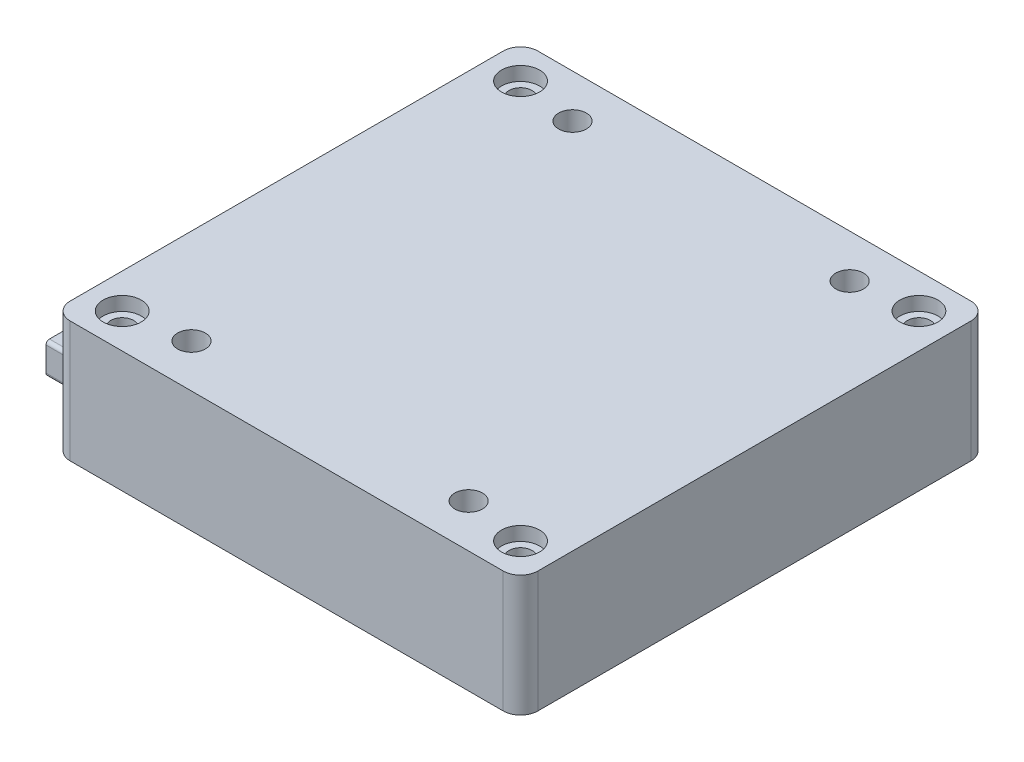
SolidWorks part; units mm, degrees
ref_plane "Front Plane" through (0, 0, 0) normal (0, 0, 1) x (1, 0, 0)
ref_plane "Top Plane" through (0, 0, 0) normal (0, 1, 0) x (1, 0, 0)
ref_plane "Right Plane" through (0, 0, 0) normal (1, 0, 0) x (0, 0, -1)
sketch "Sketch2" plane through (0, 0, 0) normal (0, 1, 0) x (1, 0, 0)
  line L1 (67.5, 67.5) -> (-67.5, 67.5)
  line L2 (67.5, 67.5) -> (67.5, -67.5)
  line L3 (67.5, -67.5) -> (-67.5, -67.5)
  line L4 (-67.5, 67.5) -> (-67.5, -67.5)
  line L5 (67.5, 67.5) -> (-67.5, -67.5) construction
  line L6 (67.5, -67.5) -> (-67.5, 67.5) construction
  point P0 (0, 0)
  dimension "D1" = 135
extrude "Boss-Extrude1" add sketch "Sketch2" along normal blind 35
fillet "Fillet1" radius 5 4 edges at (67.5, 17.5, -67.5) (67.5, 17.5, 67.5) (-67.5, 17.5, 67.5) (-67.5, 17.5, -67.5)
hole_wizard "CBORE for M6 Hex Head Bolt1" positions "3DSketch1" profile "Sketch6" counterbore size "M6" standard "DIN"
sketch3d "3DSketch1"
  line L0 (62.5, 35, -67.5) -> (-62.5, 35, -67.5) construction
  line L1 (-67.5, 35, -62.5) -> (-67.5, 35, 62.5) construction
  point P0 (-57.5, 35, -57.5)
  dimension "D1" = 10
  dimension "D2" = 10
sketch "Sketch6" plane through (-57.5, 35, -57.5) normal (1, 0, 0) x (0, 0, 1)
  line L0 (0, 0) -> (0, 43.9828)
  line L1 (0, 43.9828) -> (3.3, 42)
  line L2 (3.3, 42) -> (3.3, 4)
  line L3 (3.3, 4) -> (5.5, 4)
  line L4 (5.5, 4) -> (5.5, 0)
  line L5 (5.5, 0) -> (0, 0)
  line L10 (0, 43.9828) -> (-3.3, 42) construction
  line L11 (0, -6.35) -> (0, 107.95) construction
  dimension "Hole Dia." = 6.6
  dimension "Hole Depth" = 42
  dimension "C'Bore Dia." = 11
  dimension "C'Bore Depth" = 4
  dimension "Drill Angle" = 118
ref_axis "Axis1" through (0, -1.75, 0) along (0, 1, 0)
sketch "Sketch7" plane through (-67.5, 0, 0) normal (-1, 0, 0) x (0, 0, 1)
  line L0 (0, -1.75) -> (0, 36.75) construction
  line L1 (60, 19) -> (-60, 19)
  line L2 (60, 19) -> (60, 5)
  line L3 (60, 5) -> (-60, 5)
  line L4 (-60, 19) -> (-60, 5)
  line L5 (60, 19) -> (-60, 5) construction
  line L6 (60, 5) -> (-60, 19) construction
  line L7 (-62.5, 0) -> (62.5, 0) construction
  point P0 (0, 12)
  dimension "D1" = 5
  dimension "D2" = 120
  dimension "D3" = 14
extrude "Boss-Extrude2" add sketch "Sketch7" along normal blind 2 separate body
fillet "Fillet2" radius 2 4 edges at (-68.5, 5, -60) (-68.5, 5, 60) (-68.5, 19, 60) (-68.5, 19, -60)
sketch "Sketch9" plane through (-69.5, 0, 0) normal (-1, 0, 0) x (0, 0, 1)
  line L0 (0, 19) -> (0, 5) construction
  line L1 (58, 19) -> (-58, 19) construction
  line L2 (-58, 5) -> (58, 5) construction
  line L3 (56.5, 15.5) -> (-56.5, 15.5)
  line L4 (56.5, 16.5) -> (-56.5, 16.5)
  line L5 (57.5, 15.5) -> (57.5, 8.5)
  line L6 (56.5, 7.5) -> (-56.5, 7.5)
  line L7 (-57.5, 15.5) -> (-57.5, 8.5)
  line L8 (57.5, 16.5) -> (-57.5, 7.5) construction
  line L9 (57.5, 7.5) -> (-57.5, 16.5) construction
  line L10 (-56.5, 15.5) -> (-56.5, 8.5)
  line L11 (56.5, 8.5) -> (-56.5, 8.5)
  line L12 (56.5, 15.5) -> (56.5, 8.5)
  arc A0 (56.5, 16.5) -> (57.5, 15.5) centre (56.5, 15.5) cw
  arc A1 (57.5, 8.5) -> (56.5, 7.5) centre (56.5, 8.5) cw
  arc A2 (-56.5, 7.5) -> (-57.5, 8.5) centre (-56.5, 8.5) cw
  arc A3 (-56.5, 16.5) -> (-57.5, 15.5) centre (-56.5, 15.5) ccw
  arc A4 (-56.5, 15.5) -> (-56.5, 15.5) centre (-56.5, 15.5) ccw
  arc A5 (-56.5, 8.5) -> (-56.5, 8.5) centre (-56.5, 8.5) cw
  arc A6 (56.5, 8.5) -> (56.5, 8.5) centre (56.5, 8.5) cw
  arc A7 (56.5, 15.5) -> (56.5, 15.5) centre (56.5, 15.5) cw
  point P6 (0, 12)
  dimension "D3" = 1
  dimension "D1" = 9
  dimension "D2" = 115
  dimension "D4" = 1
extrude "Boss-Extrude3" add sketch "Sketch9" along normal blind 10
sketch "Sketch12" plane through (0, 35, 0) normal (0, 1, 0) x (1, 0, 0)
  circle A0 centre (-40, 55) radius 4
  dimension "D1" = 8
  dimension "D2" = 55
  dimension "D3" = 40
extrude "Cut-Extrude1" cut sketch "Sketch12" against normal blind 10
mirror "Mirror3" about plane through (0, 0, 0) normal (0, 0, 1) of "CBORE for M6 Hex Head Bolt1", "Cut-Extrude1"
mirror "Mirror4" about plane through (0, 0, 0) normal (1, 0, 0) of "Mirror3"
